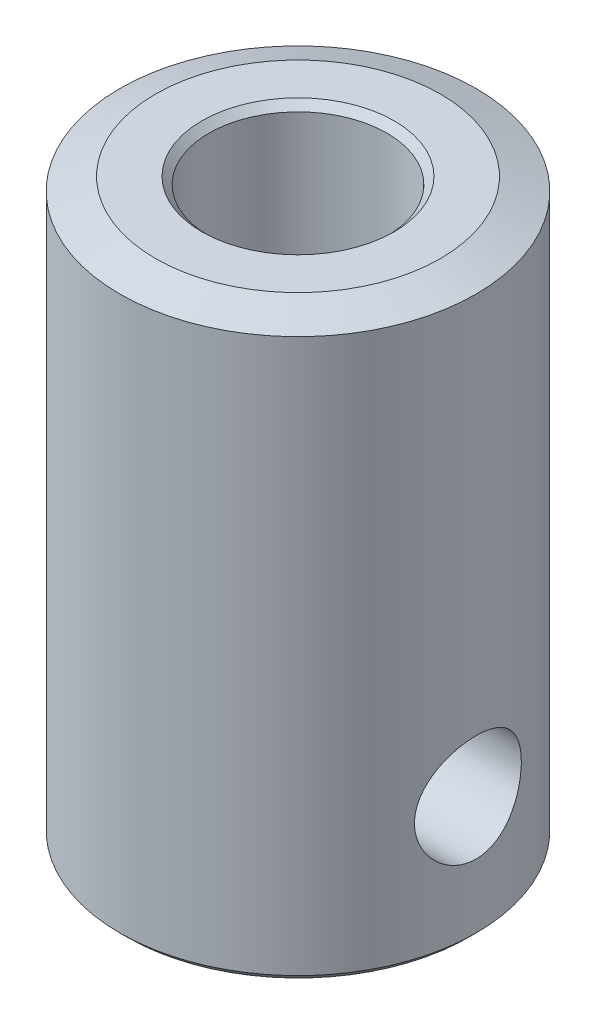
SolidWorks part; units mm, degrees
material "1060 Alloy"
ref_plane "Front Plane" through (0, 0, 0) normal (0, 0, 1) x (1, 0, 0)
ref_plane "Top Plane" through (0, 0, 0) normal (0, 1, 0) x (1, 0, 0)
ref_plane "Right Plane" through (0, 0, 0) normal (1, 0, 0) x (0, 0, -1)
sketch "Sketch1" plane through (0, 0, 0) normal (0, 1, 0) x (1, 0, 0)
  circle A0 centre (0, 0) radius 5
  circle A1 centre (0, 0) radius 2.5
  dimension "D1" = 10
  dimension "D2" = 5
extrude "Boss-Extrude1" add sketch "Sketch1" along normal blind 16.1
chamfer "Chamfer1" distance 0.2 angle 45 3 edges at (0, 0, 2.5) (0, 0, 5) (0, 16.1, 2.5)
chamfer "Chamfer2" distance 1 angle 20 1 edges at (0, 16.1, 5) first distance on face at (0, 16.1, 2.7)
ref_plane "Plane1" through (0, 0, -5) normal (0, 0, -1) x (-1, 0, 0)
sketch "Sketch2" plane through (0, 0, -5) normal (0, 0, -1) x (-1, 0, 0)
  line L0 (0, 0) -> (0, 3.5) construction
  circle A0 centre (0, 3.5) radius 1.5
  dimension "D2" = 3
  dimension "D1" = 3.5
extrude "Cut-Extrude1" cut sketch "Sketch2" against normal up to next
ref_axis "Axis1" through (0, 15.9, 0) along (0, -1, 0)
pattern_circular "CirPattern1" count 2 every 90 about axis through (0, 15.9, 0) along (0, -1, 0) of "Cut-Extrude1"
